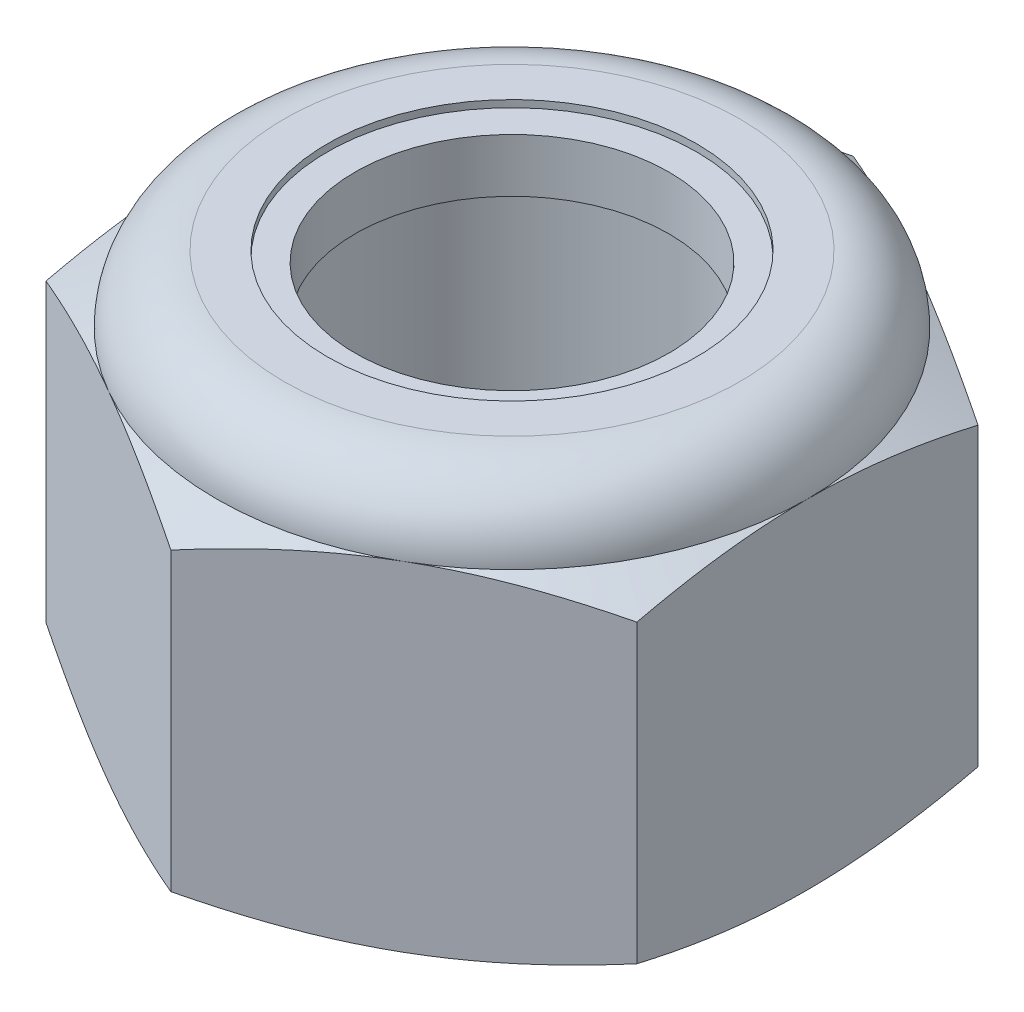
SolidWorks part; units mm, degrees
ref_plane "Front" through (0, 0, 0) normal (0, 0, 1) x (1, 0, 0)
ref_plane "Top" through (0, 0, 0) normal (0, 1, 0) x (1, 0, 0)
ref_plane "Right" through (0, 0, 0) normal (1, 0, 0) x (0, 0, -1)
sketch "Sketch1" plane through (0, 0, 0) normal (1, 0, 0) x (0, 0, -1)
  line L0 (0, 0) -> (0, 8.7312) construction
  line L1 (6.35, 0) -> (-6.35, 0) construction
  line L2 (-3.9688, 8.7312) -> (3.9688, 8.7312) construction
  line L3 (3.9688, 8.7312) -> (3.9687, 7.3201) construction
  point P9 (-3.9688, 8.7312)
  point P10 (3.9688, 8.7312)
  point P11 (6.35, 0)
  dimension "Height" = 8.7312
  dimension "Hex Flats" = 12.7
  dimension "Thread Dia" = 7.9375
  dimension "Thread Pitch" = 1.4111
sketch "Sketch13" plane through (0, 0, 0) normal (0, 1, 0) x (1, 0, 0)
  line L1 (0, 7.3323) -> (-6.35, 3.6662)
  line L2 (-6.35, 3.6662) -> (-6.35, -3.6662)
  line L3 (-6.35, -3.6662) -> (0, -7.3323)
  line L4 (0, -7.3323) -> (6.35, -3.6662)
  line L5 (6.35, -3.6662) -> (6.35, 3.6662)
  line L6 (6.35, 3.6662) -> (0, 7.3323)
  circle A0 centre (0, 0) radius 6.35 construction
  circle A1 centre (0, 0) radius 3.9688
  point P11 (0, -3.9688)
  point P13 (0, 3.9688)
extrude "Extrude1" add sketch "Sketch13" along normal up to vertex (8.7312 mm away) up to point (0, 8.7312, 0)
sketch "Sketch5" plane through (0, 0, 0) normal (1, 0, 0) x (0, 0, -1)
  line L0 (0, 0) -> (6.35, 0)
  line L1 (6.35, 0) -> (7.3323, 0.4581)
  line L2 (7.3323, 0.4581) -> (7.3323, 6.818)
  line L3 (7.3323, 6.818) -> (6.35, 7.276)
  line L4 (4.8948, 8.7312) -> (4.8948, 10.0013)
  line L5 (4.8948, 10.0013) -> (8.6023, 10.0013)
  line L6 (8.6023, 10.0013) -> (8.6023, -1.27)
  line L7 (8.6023, -1.27) -> (0, -1.27)
  line L8 (0, -1.27) -> (0, 0)
  line L9 (6.35, 7.276) -> (6.35, 0) construction
  line L12 (7.3323, 8.7312) -> (7.3323, 0) construction
  line L13 (7.3323, 4.3656) -> (8.6023, 4.3656) construction
  line L15 (0, 0) -> (0, 10.0013) construction
  line L18 (6.35, 0) -> (-6.35, 0) construction
  line L19 (3.6662, 8.7312) -> (7.3323, 8.7312) construction
  line L20 (0, 10.0013) -> (4.8948, 10.0013) construction
  line L21 (3.6662, 0) -> (7.3323, 0) construction
  arc A0 (6.35, 7.276) -> (4.8948, 8.7312) centre (4.8948, 7.276) ccw
  dimension "D1" = 25
  dimension "D2" = 1.27
  dimension "D4" = 1.4552
revolve "Cut-Revolve3" cut sketch "Sketch5" angle 360 about L15
sketch "Sketch4" plane through (0, 0, 0) normal (1, 0, 0) x (0, 0, -1)
  line L0 (0, 7.276) -> (4.3656, 7.276)
  line L1 (4.3656, 7.276) -> (0, 5.2403)
  line L3 (0, 2.0357) -> (4.3656, 0)
  line L4 (4.3656, 0) -> (0, 0)
  line L5 (0, 0) -> (0, 7.276) construction
  line L10 (0, 0) -> (0, 8.7312) construction
  line L11 (0, 2.0357) -> (0, 0)
  line L12 (0, 7.276) -> (0, 5.2403)
  line L13 (5.4993, 7.276) -> (0, 7.276) construction
  dimension "D1" = 25
  dimension "D2" = 8.7312
sketch "Sketch6" plane through (0, 0, 0) normal (1, 0, 0) x (0, 0, -1)
  line L0 (0, 7.276) -> (6.1976, 7.276)
  line L1 (4.8948, 8.5788) -> (2.4474, 8.5788)
  line L2 (0, 10.0013) -> (0, 7.276)
  line L3 (2.4474, 10.0013) -> (0, 10.0013)
  line L4 (0, 10.0013) -> (4.8948, 10.0013) construction
  line L5 (0, 0) -> (0, 10.0013) construction
  line L6 (0, 10.0013) -> (0, 0) construction
  line L7 (2.4474, 8.5788) -> (2.4474, 10.0013)
  line L8 (4.8948, 8.7312) -> (4.8948, 8.5788) construction
  line L9 (2.4474, 8.5788) -> (0, 8.5788) construction
  line L10 (0, 8.5788) -> (0, 5.2403) construction
  arc A0 (6.1976, 7.276) -> (4.8948, 8.5788) centre (4.8948, 7.276) ccw
  arc A1 (6.35, 7.276) -> (4.8948, 8.7312) centre (4.8948, 7.276) ccw construction
  dimension "D1" = 0.1524
revolve "Cut-Revolve4" cut sketch "Sketch6" angle 360 about L6
revolve "Cut-Revolve2" cut sketch "Sketch4" angle 360 about L5
sketch "Sketch7" plane through (0, 0, 0) normal (1, 0, 0) x (0, 0, -1)
  line L0 (3.3734, 7.3522) -> (6.119, 7.3522)
  line L1 (4.8948, 8.5027) -> (3.3734, 8.5027)
  line L2 (3.3734, 8.5027) -> (3.3734, 7.3522)
  line L3 (3.3734, 7.3522) -> (0, 7.3522) construction
  line L4 (0, 7.3522) -> (0, 8.5027) construction
  line L5 (0, 8.5027) -> (3.3734, 8.5027) construction
  line L6 (3.3734, 7.3522) -> (3.3734, 7.276) construction
  line L7 (0, 7.276) -> (6.1976, 7.276) construction
  line L8 (4.8948, 8.5027) -> (4.8948, 8.5788) construction
  arc A0 (6.119, 7.3522) -> (4.8948, 8.5027) centre (4.8948, 7.276) ccw
  arc A2 (6.1976, 7.276) -> (4.8948, 8.5788) centre (4.8948, 7.276) ccw construction
  point P15 (3.3734, 8.5027)
  point P18 (-4.1341, 8.5027)
  point P19 (4.1341, 8.5027)
  dimension "D1" = 0.0762
  dimension "D2" = 6.7469
revolve "Revolve2" add sketch "Sketch7" angle 360 about L4
sketch "Sketch2" [suppressed] plane through (0, 0, 0) normal (1, 0, 0) x (0, 0, -1)
  line L0 (-3.9688, 0) -> (-3.9688, 7.276) construction
  line L1 (0, 0) -> (3.9688, 0)
  line L2 (0, 0) -> (0, 7.276)
  line L3 (0, 7.276) -> (3.9688, 7.276)
  line L4 (3.9688, 0) -> (3.9688, 7.276)
  line L6 (5.4993, 7.276) -> (6.35, 7.276) construction
  line L7 (0, -3.9688) -> (0, 0) construction
revolve "Revolve1" [suppressed] add sketch "Sketch2" angle 360 about L7
sketch "Sketch9" [suppressed] plane through (0, 0, 0) normal (1, 0, 0) x (0, 0, -1)
  line L0 (4.1215, 8.599) -> (4.1215, 7.1878) construction
  line L1 (4.1215, 7.1878) -> (2.8994, 7.8934) construction
  line L2 (2.8994, 7.8934) -> (4.1215, 8.599) construction
  line L3 (3.0522, 7.9816) -> (3.0522, 7.8052) construction
  line L4 (3.9688, 8.5108) -> (3.9688, 7.276) construction
  line L5 (2.8994, 7.8934) -> (3.0522, 7.8934) construction
  line L6 (3.9687, 7.8934) -> (4.1215, 7.8934) construction
  line L7 (4.0451, 7.8934) -> (4.0451, 8.5549) construction
  line L8 (4.1215, 7.1878) -> (4.0451, 8.5549)
  line L9 (4.0451, 8.5549) -> (3.0522, 7.9816)
  line L10 (3.0522, 7.9816) -> (3.0522, 7.8052)
  line L11 (3.0522, 7.8052) -> (4.1215, 7.1878)
  dimension "D1" = 1.4111
sketch "Sketch10" [suppressed] plane through (0, 7.276, 0) normal (0, 1, 0) x (1, 0, 0)
  circle A1 centre (0, 0) radius 3.9688
  circle A2 centre (0, 0) radius 3.9688
  dimension "D1" = 0
curve "Helix/Spiral1" [suppressed] pitch 1.4111 height 10.1424 turns 7.1875
sweep "Cut-Sweep1" [suppressed] cut profiles "Sketch9" path "Helix/Spiral1"
sketch "Sketch11" [suppressed] plane through (0, 0, 0) normal (1, 0, 0) x (0, 0, -1)
  line L0 (0, 0) -> (0, 8.7312) construction
  line L1 (6.35, 0) -> (-6.35, 0) construction
  line L4 (0, 8.7312) -> (0, 0) construction
  line L5 (0, 4.3656) -> (3.9688, 4.3656) construction
  line L6 (0, 0) -> (4.3656, 0)
  line L7 (0, 2.0357) -> (0, 0)
  line L8 (4.3656, 0) -> (0, 2.0357)
  dimension "D1" = 8.7312
  dimension "D2" = 25
revolve "Revolve3" [suppressed] add sketch "Sketch11" angle 360 about L4
sketch "Sketch12" [suppressed] plane through (0, 0, 0) normal (1, 0, 0) x (0, 0, -1)
  line L0 (4.3656, 7.276) -> (0, 7.276)
  line L1 (0, 7.276) -> (0, 0)
  line L2 (0, 0) -> (4.3656, 0)
  line L3 (6.35, 0) -> (-6.35, 0) construction
  line L4 (4.3656, 0) -> (4.3656, 7.276)
  line L5 (-4.3656, 0) -> (4.3656, 0) construction
revolve "Revolve4" [suppressed] add sketch "Sketch12" angle 360 about L0
combine bodies "Combine1" [suppressed] operation type subtract main body 136 bodies to subtract 133
equation "\"D4@Sketch5\" = \"Height@Sketch1\" / 6"
equation "\"D1@Sketch9\" = \"Thread Pitch@Sketch1\""
equation "\"D2@Sketch9\" = \"Thread Pitch@Sketch1\" / 8"
equation "\"D4@Helix/Spiral1\" = \"Thread Pitch@Sketch1\""
equation "\"D3@Helix/Spiral1\" = \"Thread Pitch@Sketch1\" + \"Height@Sketch1\""
equation "\"D2@Sketch4\" = \"Thread Dia@Sketch1\" * 1.1"
equation "\"D1@Sketch11\" = \"Thread Dia@Sketch1\" * 1.1"
equation "\"D2@Sketch7\" = \"Thread Dia@Sketch1\" * .85"
